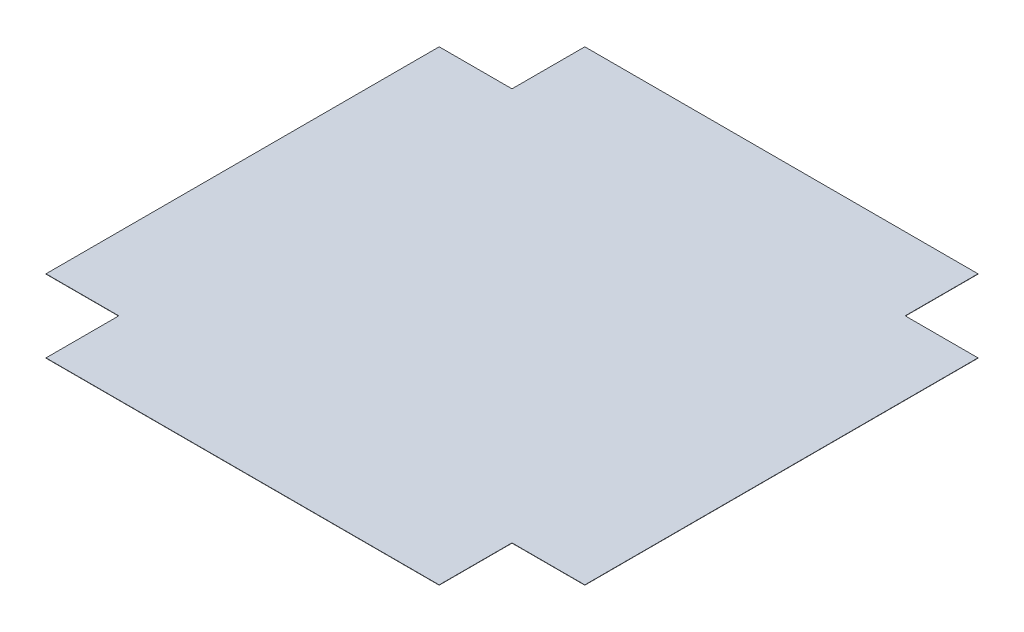
SolidWorks part; units mm, degrees
material "Corrugated Paper"
ref_plane "Front" through (0, 0, 0) normal (0, 0, 1) x (1, 0, 0)
ref_plane "Top" through (0, 0, 0) normal (0, 1, 0) x (1, 0, 0)
ref_plane "Right" through (0, 0, 0) normal (1, 0, 0) x (0, 0, -1)
ref_axis "X" through (-80.9, 0, 0) along (1, 0, 0)
ref_axis "Y" through (0, -50, 0) along (0, 1, 0)
ref_axis "Z" through (0, 0, -80.9) along (0, 0, 1)
sketch "Sketch1" plane through (0, 0, 0) normal (0, 1, 0) x (1, 0, 0)
  line L0 (-67.5, 92.5) -> (67.5, 92.5)
  line L1 (67.5, 92.5) -> (67.5, 67.5)
  line L2 (67.5, 67.5) -> (92.5, 67.5)
  line L3 (92.5, 67.5) -> (92.5, -67.5)
  line L4 (92.5, -67.5) -> (67.5, -67.5)
  line L5 (67.5, -67.5) -> (67.5, -92.5)
  line L6 (67.5, -92.5) -> (-67.5, -92.5)
  line L7 (-67.5, -92.5) -> (-67.5, -67.5)
  line L8 (-67.5, -67.5) -> (-92.5, -67.5)
  line L9 (-92.5, -67.5) -> (-92.5, 67.5)
  line L10 (-92.5, 67.5) -> (-67.5, 67.5)
  line L11 (-67.5, 67.5) -> (-67.5, 92.5)
  line L12 (-92.5, 0) -> (92.5, 0) construction
  line L13 (0, 92.5) -> (0, -92.5) construction
  dimension "D1" = 185
  dimension "D2" = 185
  dimension "D3" = 25
  dimension "D4" = 25
extrude "Boss-Extrude1" add sketch "Sketch1" along normal mid plane 0.1
